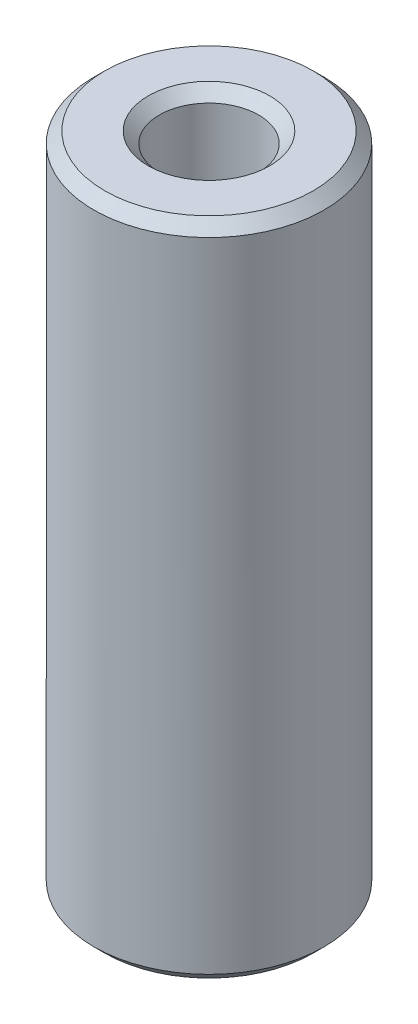
SolidWorks part; units mm, degrees
ref_plane "Front Plane" through (0, 0, 0) normal (0, 0, 1) x (1, 0, 0)
ref_plane "Top Plane" through (0, 0, 0) normal (0, 1, 0) x (1, 0, 0)
ref_plane "Right Plane" through (0, 0, 0) normal (1, 0, 0) x (0, 0, -1)
sketch "Sketch1" plane through (0, 0, 0) normal (0, 1, 0) x (1, 0, 0)
  circle A0 centre (0, 0) radius 10
  dimension "SLEEVE_OD" = 20
extrude "Boss-Extrude1" add sketch "Sketch1" along normal blind 57.3547
sketch "Sketch2" plane through (0, 0, 0) normal (0, 1, 0) x (1, 0, 0)
  circle A0 centre (0, 0) radius 4.3151
  dimension "BORE_D" = 8.6302
extrude "Cut-Extrude1" cut sketch "Sketch2" along normal through all
chamfer "Chamfer1" distance 0.9595 angle 45 4 edges at (0, 57.3547, 4.3151) (0, 0, 4.3151) (0, 0, 10) (0, 57.3547, 10)
